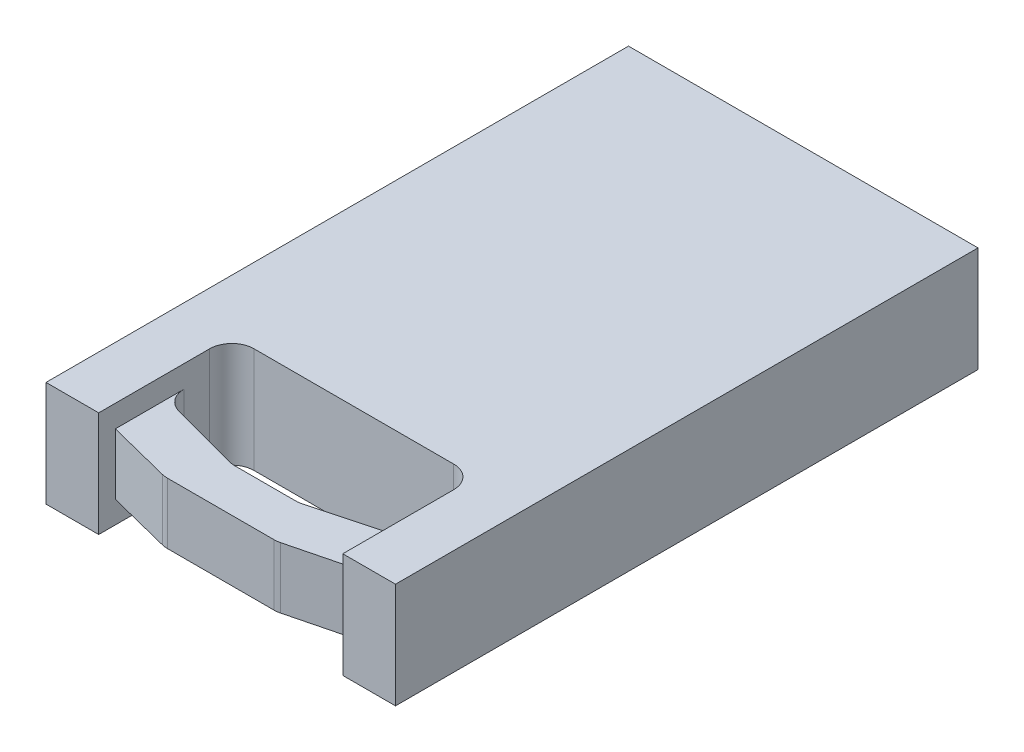
SolidWorks part; units mm, degrees
ref_plane "Front Plane" through (0, 0, 0) normal (0, 0, 1) x (1, 0, 0)
ref_plane "Top Plane" through (0, 0, 0) normal (0, 1, 0) x (1, 0, 0)
ref_plane "Right Plane" through (0, 0, 0) normal (1, 0, 0) x (0, 0, -1)
sketch "Sketch1" plane through (0, 0, 0) normal (0, 1, 0) x (1, 0, 0)
  line L1 (-209.55, -166.6875) -> (209.55, -166.6875)
  line L2 (-209.55, -166.6875) -> (-209.55, 166.6875)
  line L3 (-209.55, 166.6875) -> (209.55, 166.6875)
  line L4 (209.55, -166.6875) -> (209.55, 166.6875)
  line L5 (-209.55, -166.6875) -> (209.55, 166.6875) construction
  line L6 (-209.55, 166.6875) -> (209.55, -166.6875) construction
  point P0 (0, 0)
  dimension "D1" = 333.375
  dimension "D2" = 419.1
extrude "Boss-Extrude1" add sketch "Sketch1" along normal blind 60.325
sketch "Sketch2" plane through (0, 60.325, 0) normal (0, 1, 0) x (1, 0, 0)
  line L0 (0, 0) -> (0, -115.8875) construction
  line L1 (-69.85, -141.2875) -> (69.85, -141.2875)
  line L2 (-69.85, -141.2875) -> (-69.85, -90.4875)
  line L3 (-69.85, -90.4875) -> (69.85, -90.4875)
  line L4 (69.85, -141.2875) -> (69.85, -90.4875)
  line L5 (-69.85, -141.2875) -> (69.85, -90.4875) construction
  line L6 (-69.85, -90.4875) -> (69.85, -141.2875) construction
  line L7 (-209.55, -166.6875) -> (209.55, -166.6875) construction
  line L8 (-69.85, -166.6875) -> (-69.85, -157.1625)
  line L9 (-69.85, -157.1625) -> (-32.169, -166.6875)
  line L10 (-32.169, -166.6875) -> (-69.85, -166.6875)
  line L11 (-69.85, -157.1625) -> (-69.85, -141.2875) construction
  line L12 (0, -166.6875) -> (0, -141.2875) construction
  line L13 (69.85, -157.1625) -> (69.85, -141.2875) construction
  line L14 (32.169, -166.6875) -> (69.85, -166.6875)
  line L15 (69.85, -157.1625) -> (32.169, -166.6875)
  line L16 (69.85, -166.6875) -> (69.85, -157.1625)
  point P0 (0, -115.8875)
  dimension "D1" = 139.7
  dimension "D2" = 50.8
  dimension "D3" = 50.8
  dimension "D4" = 9.525
extrude "Cut-Extrude1" cut sketch "Sketch2" against normal through all
chamfer "Chamfer1" distance 50.8 angle 15 2 edges at (69.85, 30.1625, 141.2875) (-69.85, 30.1625, 141.2875) first distance on face at (0, 30.1625, 141.2875)
fillet "Fillet1" radius 12.7 8 edges at (32.169, 30.1625, 166.6875) (-32.169, 30.1625, 166.6875) (69.85, 30.1625, 127.6757) (19.05, 30.1625, 141.2875) (-19.05, 30.1625, 141.2875) (-69.85, 30.1625, 127.6757) (69.85, 30.1625, 90.4875) (-69.85, 30.1625, 90.4875)
sketch "Sketch3" plane through (0, 60.325, 0) normal (0, 1, 0) x (1, 0, 0)
  line L1 (-69.85, -166.6875) -> (69.85, -166.6875)
  line L2 (-69.85, -166.6875) -> (-69.85, -110.2845)
  line L3 (-69.85, -110.2845) -> (69.85, -110.2845)
  line L4 (69.85, -166.6875) -> (69.85, -110.2845)
extrude "Cut-Extrude2" cut sketch "Sketch3" against normal blind 12.7
sketch "Sketch4" plane through (0, 0, 0) normal (0, -1, 0) x (1, 0, 0)
  line L0 (69.85, 117.9306) -> (69.85, 103.1875) construction
  line L1 (-69.85, 166.6875) -> (69.85, 166.6875)
  line L2 (-69.85, 166.6875) -> (-69.85, 110.5591)
  line L3 (-69.85, 110.5591) -> (69.85, 110.5591)
  line L4 (69.85, 166.6875) -> (69.85, 110.5591)
extrude "Cut-Extrude3" cut sketch "Sketch4" against normal blind 12.7
sketch "Sketch5" plane through (0, 60.325, 0) normal (0, 1, 0) x (1, 0, 0)
  line L0 (209.55, 166.6875) -> (-209.55, 166.6875) construction
  line L1 (-100.0125, -166.6875) -> (100.0125, -166.6875)
  line L2 (-100.0125, -166.6875) -> (-100.0125, 166.6875)
  line L3 (-100.0125, 166.6875) -> (100.0125, 166.6875)
  line L4 (100.0125, -166.6875) -> (100.0125, 166.6875)
  line L5 (-100.0125, -166.6875) -> (100.0125, 166.6875) construction
  line L6 (-100.0125, 166.6875) -> (100.0125, -166.6875) construction
  point P0 (0, 0)
  dimension "D1" = 200.025
extrude "Cut-Extrude4" cut sketch "Sketch5" against normal through all flip side to cut
